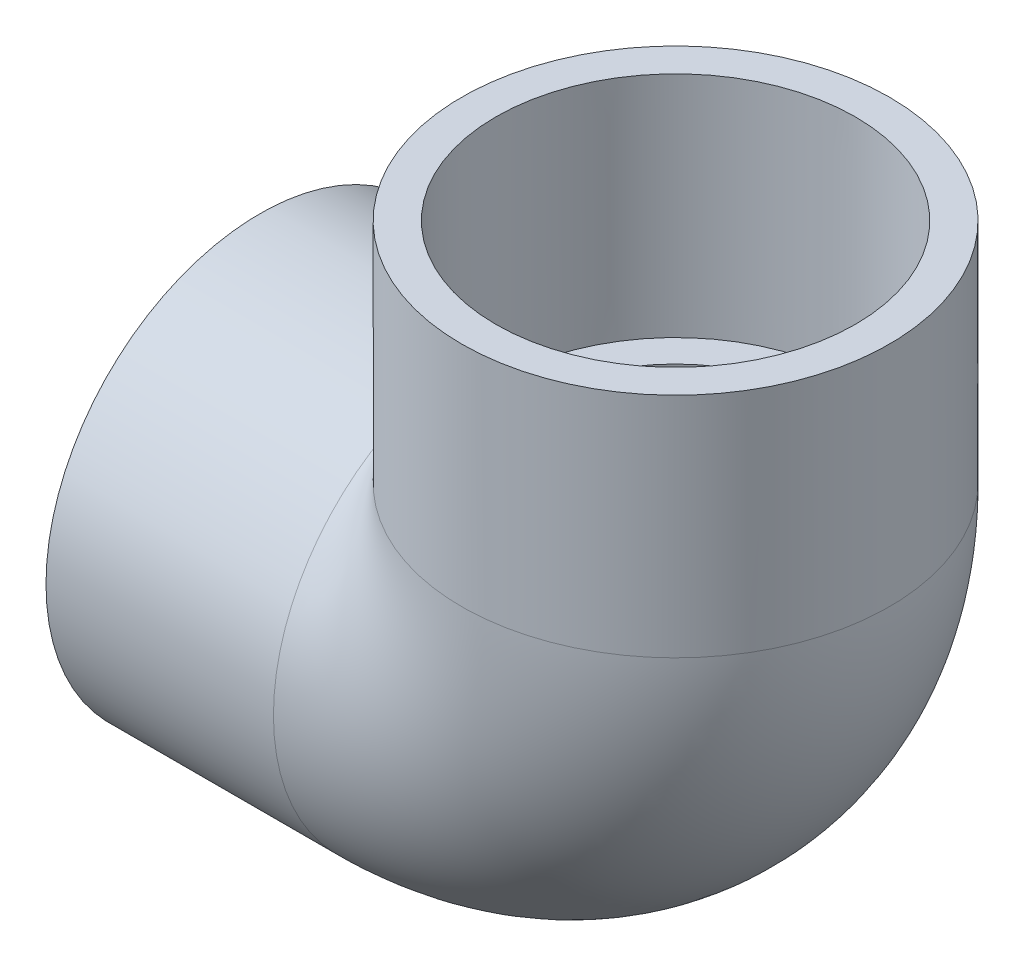
SolidWorks part; units mm, degrees
ref_plane "Front Plane" through (0, 0, 0) normal (0, 0, 1) x (1, 0, 0)
ref_plane "Top Plane" through (0, 0, 0) normal (0, 1, 0) x (1, 0, 0)
ref_plane "Right Plane" through (0, 0, 0) normal (1, 0, 0) x (0, 0, -1)
sketch "ElbowArc" plane through (0, 0, 0) normal (0, 0, 1) x (1, 0, 0)
  line L0 (-70.104, 0) -> (0, 0) construction
  line L1 (0, 0) -> (0, 70.104) construction
  line L2 (-31.75, 0) -> (0, 0) construction
  line L3 (0, 0) -> (0, 31.75) construction
  line L4 (-70.104, 36.068) -> (-70.104, -36.068) construction
  line L5 (-31.75, 30.0863) -> (-70.104, 30.3149) construction
  line L6 (-31.75, 30.0863) -> (-31.75, -30.0863) construction
  line L7 (-31.75, -30.0863) -> (-70.104, -30.3149) construction
  line L8 (-70.104, 30.3149) -> (-70.104, -30.3149) construction
  line L9 (-36.068, 70.104) -> (36.068, 70.104) construction
  line L10 (-30.3149, 70.104) -> (30.3149, 70.104) construction
  line L11 (30.3149, 70.104) -> (30.0863, 31.75) construction
  line L12 (30.0863, 31.75) -> (-30.0863, 31.75) construction
  line L13 (-30.0863, 31.75) -> (-30.3149, 70.104) construction
  line L14 (-31.75, 24.6253) -> (-31.75, -24.6253) construction
  line L18 (-24.6253, 31.75) -> (24.6253, 31.75) construction
  dimension "H" = 70.104
  dimension "BendRadius" = 31.75
  dimension "M" = 72.136
  dimension "OD A" = 60.6298
  dimension "OD B" = 60.1726
  dimension "ID" = 49.2506
  dimension "BendAngle" = 90
sketch "Sketch1" plane through (0, 0, 0) normal (0, 0, 1) x (1, 0, 0)
  line L0 (-70.104, 0) -> (0, 0) construction
  line L1 (-70.104, 0) -> (0, 0) construction
  line L3 (-70.104, -36.068) -> (-31.75, -36.068)
  line L4 (-70.104, -36.068) -> (-70.104, -30.3149)
  line L5 (-70.104, -30.3149) -> (-31.75, -30.0863)
  line L6 (-31.75, -36.068) -> (-31.75, -30.0863)
revolve "Revolve1" add sketch "Sketch1" angle 360 about L1
sketch "Sketch2" plane through (0, 0, 0) normal (0, 0, 1) x (1, 0, 0)
  line L0 (30.3149, 70.104) -> (30.0863, 31.75)
  line L1 (30.0863, 31.75) -> (36.068, 31.75)
  line L2 (36.068, 31.75) -> (36.068, 70.104)
  line L3 (36.068, 70.104) -> (30.3149, 70.104)
  line L4 (0, 0) -> (0, 70.104) construction
  line L5 (0, 0) -> (0, 70.104) construction
revolve "Revolve2" add sketch "Sketch2" angle 360 about L5
sketch "Sketch3" plane through (-31.75, 0, 0) normal (1, 0, 0) x (0, 0, -1)
  circle A0 centre (0, 0) radius 24.6253
  circle A1 centre (0, 0) radius 36.068
sketch "Sketch4" plane through (0, 0, 0) normal (0, 0, 1) x (1, 0, 0)
  line L0 (-70.104, 0) -> (0, 0) construction
  line L1 (0, 0) -> (0, 70.104) construction
  line L2 (-70.104, 0) -> (-31.75, 0) construction
  line L3 (0, 31.75) -> (0, 70.104) construction
  arc A0 (-31.75, 0) -> (0, 31.75) centre (-31.75, 31.75) ccw
sweep "Sweep1" add profiles "Sketch3" path "Sketch4"
other "CPoint1" parameters "Diameter"=50.8, "StubLength"=228.6
ref_axis "Axis1" through (0, 41.75, 0) along (0, -1, 0)
other "CPoint2" parameters "Diameter"=50.8, "StubLength"=228.6
ref_axis "Axis2" through (-41.75, 0, 0) along (1, 0, 0)
other "RPoint1"
